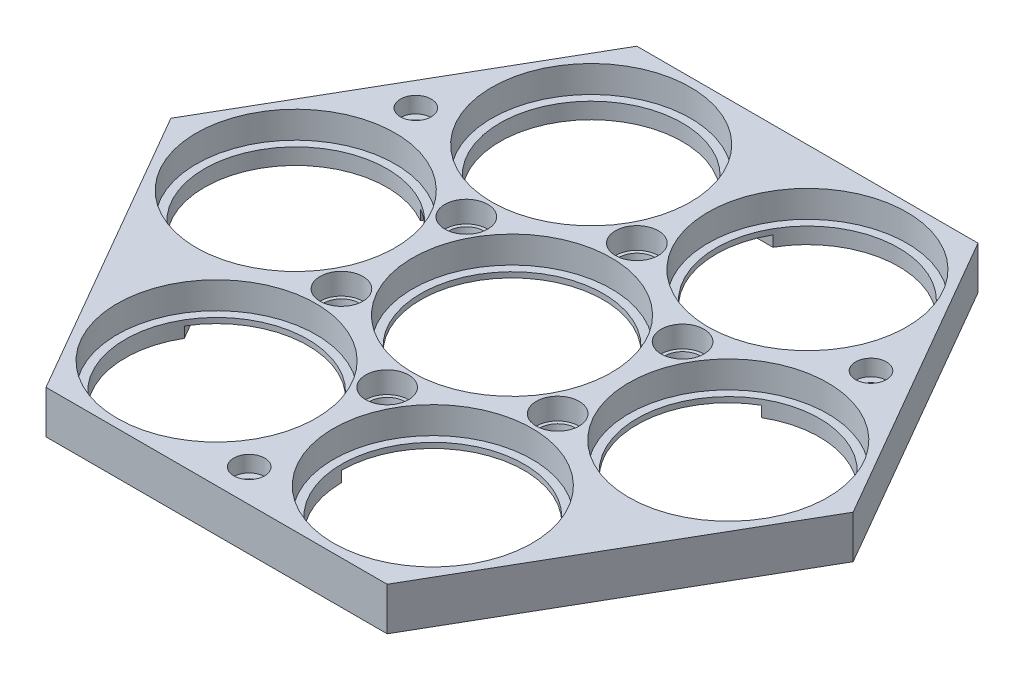
SolidWorks part; units mm, degrees
material "Malleable Cast Iron"
ref_plane "Front Plane" through (0, 0, 0) normal (0, 0, 1) x (1, 0, 0)
ref_plane "Top Plane" through (0, 0, 0) normal (0, 1, 0) x (1, 0, 0)
ref_plane "Right Plane" through (0, 0, 0) normal (1, 0, 0) x (0, 0, -1)
sketch "Sketch1" plane through (0, 0, 0) normal (0, 1, 0) x (1, 0, 0)
  line L0 (-23.3, 0) -> (-17, 0) construction
  line L1 (40.3, 0) -> (20.15, 34.9008) construction
  line L2 (20.15, 34.9008) -> (-20.15, 34.9008) construction
  line L3 (-20.15, 34.9008) -> (-40.3, 0) construction
  line L4 (-40.3, 0) -> (-20.15, -34.9008) construction
  line L5 (-20.15, -34.9008) -> (20.15, -34.9008) construction
  line L6 (20.15, -34.9008) -> (40.3, 0) construction
  line L7 (-20.15, 51.9008) -> (-20.15, 55.0508) construction
  line L8 (63.5672, 0) -> (31.7836, 55.0508)
  line L9 (31.7836, 55.0508) -> (-31.7836, 55.0508)
  line L10 (-31.7836, 55.0508) -> (-63.5672, 0)
  line L11 (-63.5672, 0) -> (-31.7836, -55.0508)
  line L12 (-31.7836, -55.0508) -> (31.7836, -55.0508)
  line L13 (31.7836, -55.0508) -> (63.5672, 0)
  line L14 (-20.15, 0) -> (-17, 0)
  circle A0 centre (0, 0) radius 17
  circle A1 centre (0, 0) radius 34.9008 construction
  circle A2 centre (-20.15, 34.9008) radius 17
  circle A3 centre (20.15, 34.9008) radius 17
  circle A4 centre (40.3, 0) radius 17
  circle A5 centre (20.15, -34.9008) radius 17
  circle A6 centre (-20.15, -34.9008) radius 17
  circle A7 centre (-40.3, 0) radius 17
  circle A8 centre (0, 0) radius 55.0508 construction
  dimension "D1" = 34
  dimension "D2" = 6.3
extrude "Boss-Extrude1" add sketch "Sketch1" along normal blind 1 contours L12 L13 L8 L9 L10 L11 A7 A6 A5 A4 A3 A2 A0 region at (46.2189, 0, 26.6845)
sketch "Sketch2" plane through (0, 1, 0) normal (0, 1, 0) x (1, 0, 0)
  line L1 (63.5672, 0) -> (31.7836, 55.0508)
  line L2 (31.7836, 55.0508) -> (-31.7836, 55.0508)
  line L3 (-31.7836, 55.0508) -> (-63.5672, 0)
  line L4 (-63.5672, 0) -> (-31.7836, -55.0508)
  line L5 (-31.7836, -55.0508) -> (31.7836, -55.0508)
  line L6 (31.7836, -55.0508) -> (63.5672, 0)
  circle A0 centre (-40.3, 0) radius 18.525
  circle A1 centre (-20.15, 34.9008) radius 18.525
  circle A2 centre (20.15, 34.9008) radius 18.525
  circle A3 centre (0, 0) radius 18.525
  circle A4 centre (40.3, 0) radius 18.525
  circle A5 centre (20.15, -34.9008) radius 18.525
  circle A6 centre (-20.15, -34.9008) radius 18.525
  circle A7 centre (0, 0) radius 55.0508 construction
  dimension "D1" = 37.05
extrude "Boss-Extrude2" add sketch "Sketch2" along normal blind 5
sketch "Sketch3" plane through (0, 6, 0) normal (0, 1, 0) x (1, 0, 0)
  line L0 (-24.2569, 9.2625) -> (-20.15, 16.3758) construction
  line L1 (-20.15, 16.3758) -> (-16.0431, 9.2625) construction
  line L2 (-16.0431, 9.2625) -> (-24.2569, 9.2625) construction
  circle A0 centre (-20.15, 11.6336) radius 4
  circle A1 centre (20.15, 11.6336) radius 4
  circle A2 centre (0, -23.2672) radius 4
  circle A3 centre (-20.15, -11.6336) radius 4
  circle A4 centre (20.15, -11.6336) radius 4
  circle A5 centre (0, 0) radius 23.2672 construction
  circle A6 centre (-40.3, 0) radius 18.525 construction
  circle A7 centre (-20.15, 34.9008) radius 18.525 construction
  circle A8 centre (0, 0) radius 18.525 construction
  circle A9 centre (0, 23.2672) radius 4
  dimension "D1" = 120
  dimension "D3" = 8
  dimension "D2" = 120
extrude "Cut-Extrude1" cut sketch "Sketch3" against normal blind 4 and the other way through all
extrude "Cut-Extrude2" cut sketch "Sketch3<2>" against normal through all draft 9 contours A0 | A1 | A2 | A3 | A4 | A9 region at (-20.15, 6, -11.6336) region at (20.15, 6, -11.6336) region at (0, 6, 23.2672) region at (-20.15, 6, 11.6336) region at (20.15, 6, 11.6336) region at (0, 6, -23.2672)
sketch "Sketch3<2>" plane through (0, 6, 0) normal (0, 1, 0) x (1, 0, 0) same geometry as "Sketch3"
sketch "Sketch4" plane through (0, 0, 0) normal (0, -1, 0) x (1, 0, 0)
  circle A0 centre (0, -23.2672) radius 4
  circle A1 centre (-20.15, 11.6336) radius 4
  circle A2 centre (20.15, 11.6336) radius 4
  circle A3 centre (0, 0) radius 23.2672 construction
  point P11 (20.15, -11.6336)
  dimension "D1" = 8
sketch "Sketch5" plane through (0, 0, 0) normal (0, -1, 0) x (1, 0, 0)
  line L0 (-63.5672, 0) -> (-31.7836, -55.0508)
  line L1 (-31.7836, -55.0508) -> (-63.5672, 0) construction
  line L3 (-28.65, -20.1784) -> (-31.8, -14.7224)
  line L4 (-63.5672, 0) -> (-57.3, 0)
  line L5 (-5.3512, -43.2672) -> (5.3512, -43.2672)
  line L6 (31.7836, -55.0508) -> (28.65, -49.6233)
  line L7 (-31.7836, -55.0508) -> (31.7836, -55.0508)
  line L8 (31.7836, 55.0508) -> (-31.7836, 55.0508)
  line L9 (-3.15, 34.9008) -> (3.15, 34.9008)
  line L10 (31.7836, 55.0508) -> (28.65, 49.6233)
  line L11 (-34.7949, 26.2679) -> (-40.1461, 16.9993)
  line L12 (-63.5672, 0) -> (-57.3, 0)
  line L13 (-31.7836, 55.0508) -> (-63.5672, 0)
  line L14 (31.7836, -55.0508) -> (63.5672, 0)
  line L15 (31.8, -14.7224) -> (28.65, -20.1784)
  line L16 (31.7836, -55.0508) -> (28.65, -49.6233)
  line L17 (40.1461, 16.9993) -> (34.7949, 26.2679)
  line L18 (31.7836, 55.0508) -> (28.65, 49.6233)
  line L19 (63.5672, 0) -> (31.7836, 55.0508)
  circle A0 centre (-20.15, -34.9008) radius 17 construction
  circle A2 centre (-40.3, 0) radius 17 construction
  arc A3 (-31.8, -14.7224) -> (-57.3, 0) centre (-40.3, 0) cw
  arc A4 (-5.3512, -43.2672) -> (-28.65, -20.1784) centre (-20.15, -34.9008) cw
  circle A5 centre (20.15, -34.9008) radius 17 construction
  arc A6 (5.3512, -43.2672) -> (28.65, -49.6233) centre (20.15, -34.9008) ccw
  circle A7 centre (0, -23.2672) radius 3.0497 construction
  arc A8 (3.15, 34.9008) -> (28.65, 49.6233) centre (20.15, 34.9008) cw
  arc A9 (-34.7949, 26.2679) -> (-3.15, 34.9008) centre (-20.15, 34.9008) cw
  arc A10 (-40.1461, 16.9993) -> (-57.3, 0) centre (-40.3, 0) ccw
  arc A11 (28.65, -20.1784) -> (28.65, -49.6233) centre (20.15, -34.9008) cw
  arc A12 (40.1461, 16.9993) -> (31.8, -14.7224) centre (40.3, 0) cw
  arc A13 (34.7949, 26.2679) -> (28.65, 49.6233) centre (20.15, 34.9008) ccw
  point P55 (0, 0)
  circle M14 centre (-40.3, 0) radius 17
  circle M15 centre (-20.15, 34.9008) radius 17
  circle M16 centre (20.15, 34.9008) radius 17
  circle M17 centre (40.3, 0) radius 17
  circle M18 centre (20.15, -34.9008) radius 17
  circle M19 centre (-20.15, -34.9008) radius 17
  line M20 (31.7836, 55.0508) -> (-31.7836, 55.0508)
  line M21 (-31.7836, 55.0508) -> (-63.5672, 0)
  line M22 (-63.5672, 0) -> (-31.7836, -55.0508)
  line M23 (-31.7836, -55.0508) -> (31.7836, -55.0508)
  line M24 (31.7836, -55.0508) -> (63.5672, 0)
  line M25 (63.5672, 0) -> (31.7836, 55.0508)
  dimension "D1" = 20
  dimension "D2" = 3
extrude "Boss-Extrude3" add sketch "Sketch5" along normal blind 2 contours L11 L9 L10 L4 M15 M16 M20 M21 M14 | L6 L5 L3 L4 M23 M18 M19 M14 M22 | L17 L15 L6 L10 M17 M18 M24 M25 M16 region at (-60.4336, 0, -1.101) region at (-46.7219, 0, 26.9749) region at (31.2171, 0, -51.7595)
sketch "Sketch6" plane through (0, 0, 0) normal (0, 1, 0) x (1, 0, 0)
  line L1 (36.7588, -6.1336) -> (3.5412, -6.1336)
  line L2 (3.5412, -6.1336) -> (-13.0675, -34.9008)
  line L3 (-13.0675, -34.9008) -> (3.5412, -63.668)
  line L4 (3.5412, -63.668) -> (36.7588, -63.668)
  line L5 (36.7588, -63.668) -> (53.3675, -34.9008)
  line L6 (53.3675, -34.9008) -> (36.7588, -6.1336)
  circle A0 centre (20.15, -34.9008) radius 28.7672 construction
  circle A1 centre (20.15, -11.6336) radius 4 construction
  dimension "D1" = 5.5
extrude "Cut-Extrude3" [suppressed] cut sketch "Sketch6" against normal through all both and the other way through all flip side to cut
sketch "Sketch7" plane through (0, 6, 0) normal (0, 1, 0) x (1, 0, 0)
  line L0 (-42.4095, 24.4851) -> (-37.1435, 27.5254) construction
  line L1 (-42.4095, 24.4851) -> (-42.4095, 18.4045) construction
  line L2 (-42.4095, 24.4851) -> (-47.6754, 27.5254) construction
  line L3 (-31.7836, 55.0508) -> (-63.5672, 0) construction
  line L4 (42.4095, 24.4851) -> (42.4095, 18.4045) construction
  line L5 (42.4095, 24.4851) -> (37.1435, 27.5254) construction
  line L6 (42.4095, 24.4851) -> (47.6754, 27.5254) construction
  line L7 (0, -48.9702) -> (-5.266, -45.9299) construction
  line L8 (0, -48.9702) -> (5.266, -45.9299) construction
  line L9 (0, -48.9702) -> (0, -55.0508) construction
  circle A0 centre (-42.4095, 24.4851) radius 2.875
  circle A1 centre (-20.15, 34.9008) radius 18.525 construction
  circle A2 centre (-40.3, 0) radius 18.525 construction
  circle A3 centre (-42.4095, 24.4851) radius 1.55
  circle A4 centre (-20.15, 34.9008) radius 18.525 construction
  circle A5 centre (42.4095, 24.4851) radius 2.875
  circle A6 centre (42.4095, 24.4851) radius 1.55
  circle A7 centre (0, -48.9702) radius 2.875
  circle A8 centre (0, -48.9702) radius 1.55
  point P33 (0, 0)
  dimension "D1" = 5.75
  dimension "D2" = 3.1
  dimension "D3" = 3
extrude "Cut-Extrude4" cut sketch "Sketch7" against normal through all contours A3 | A6 | A8 region at (-42.4095, 6, -24.4851)
extrude "Cut-Extrude5" cut sketch "Sketch7<3>" against normal blind 3 contours A0 A3 | A5 | A7 region at (-45.2031, 6, -24.4851)
sketch "Sketch7<3>" plane through (0, 6, 0) normal (0, 1, 0) x (1, 0, 0) same geometry as "Sketch7"
sketch "Sketch8" plane through (0, 6, 0) normal (0, 1, 0) x (1, 0, 0)
  line L1 (20.15, -34.9008) -> (40.3, 0) construction
  line L2 (40.3, 0) -> (20.15, 34.9008) construction
  line L3 (20.15, 34.9008) -> (-20.15, 34.9008) construction
  line L4 (-20.15, 34.9008) -> (-40.3, 0) construction
  line L5 (-40.3, 0) -> (-20.15, -34.9008) construction
  line L6 (-20.15, -34.9008) -> (20.15, -34.9008) construction
  circle A0 centre (0, 0) radius 34.9008 construction
  dimension "D1" = 69.8016
